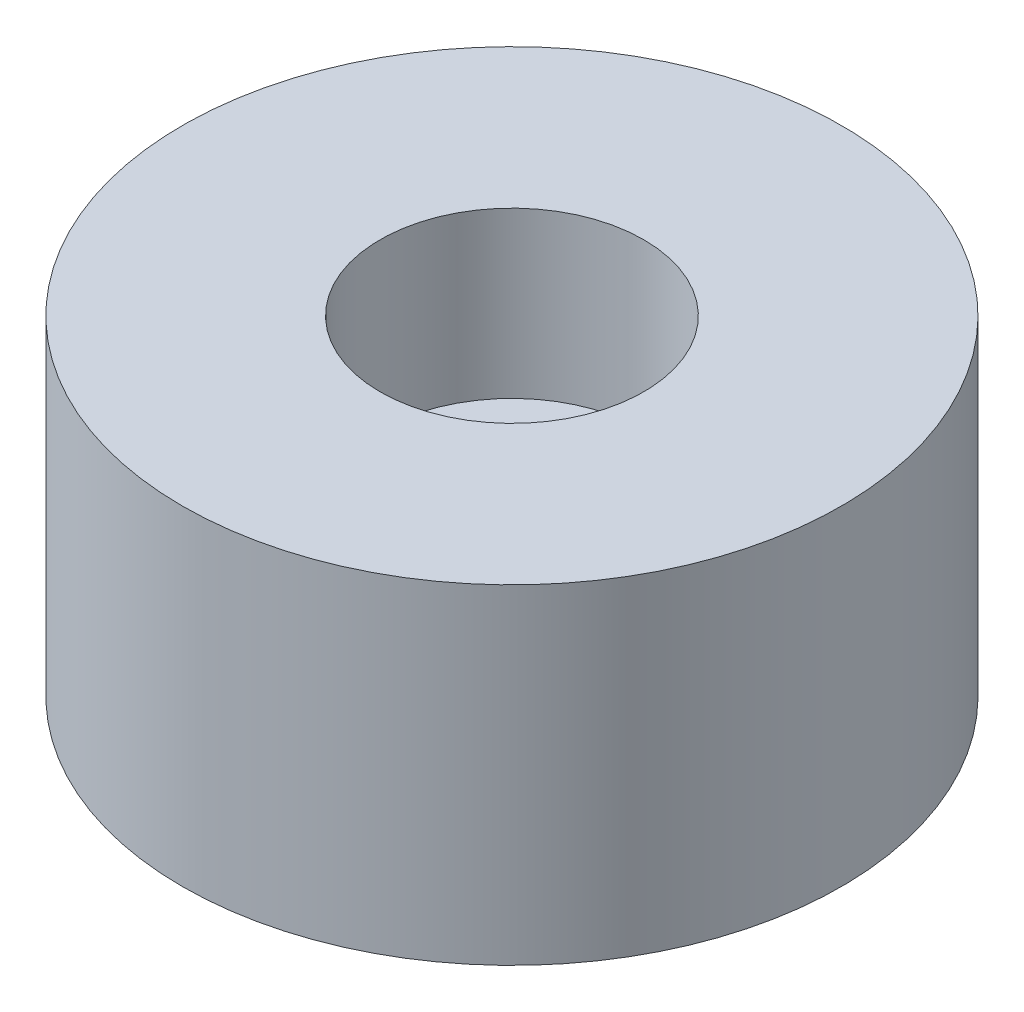
SolidWorks part; units mm, degrees
ref_plane "Front Plane" through (0, 0, 0) normal (0, 0, 1) x (1, 0, 0)
ref_plane "Top Plane" through (0, 0, 0) normal (0, 1, 0) x (1, 0, 0)
ref_plane "Right Plane" through (0, 0, 0) normal (1, 0, 0) x (0, 0, -1)
sketch "Sketch1" plane through (0, 0, 0) normal (0, 1, 0) x (1, 0, 0)
  circle A0 centre (0, 0) radius 4
  dimension "D1" = 8
extrude "Boss-Extrude1" add sketch "Sketch1" along normal blind 4
sketch "Sketch2" plane through (0, 4, 0) normal (0, 1, 0) x (1, 0, 0)
  circle A0 centre (0, 0) radius 1.6
  dimension "D1" = 3.2
extrude "Cut-Extrude1" cut sketch "Sketch2" against normal blind 2
